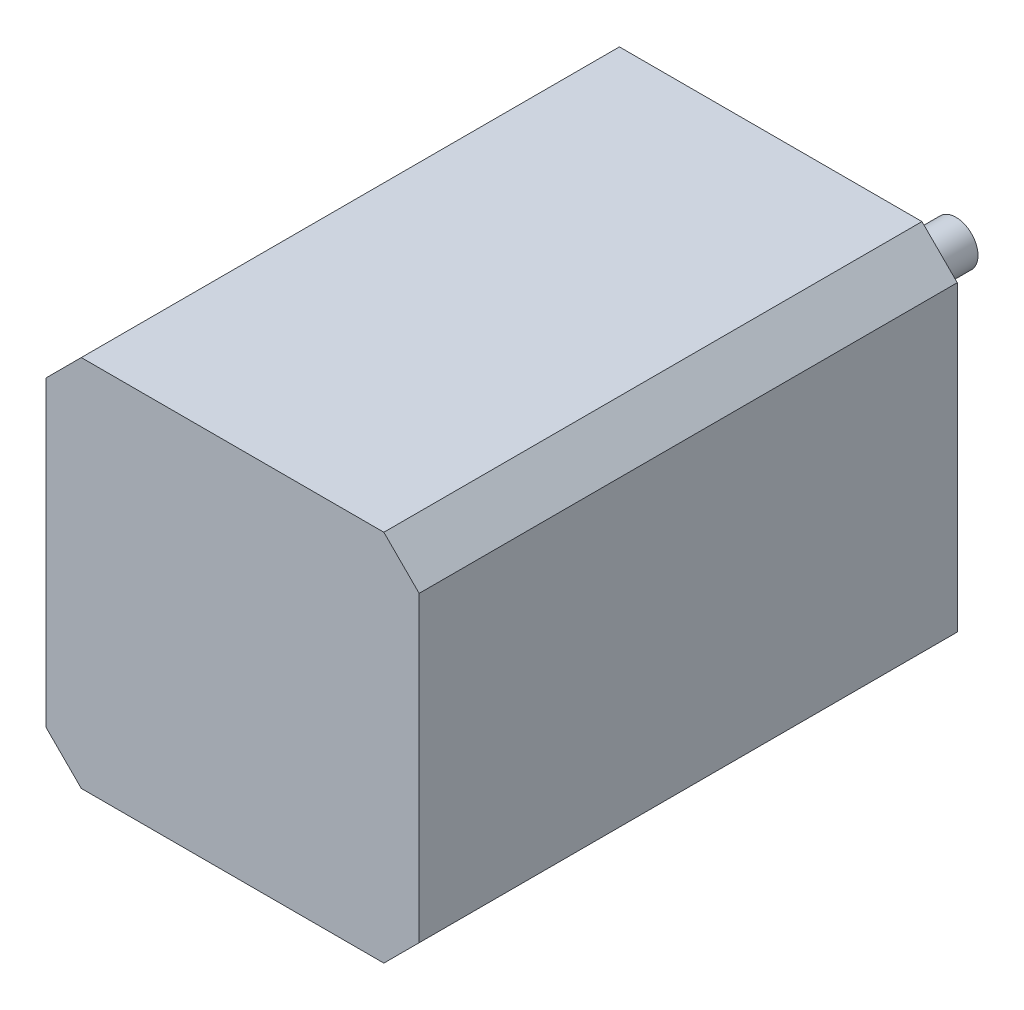
SolidWorks part; units mm, degrees
ref_plane "Front Plane" through (0, 0, 0) normal (0, 0, 1) x (1, 0, 0)
ref_plane "Top Plane" through (0, 0, 0) normal (0, 1, 0) x (1, 0, 0)
ref_plane "Right Plane" through (0, 0, 0) normal (1, 0, 0) x (0, 0, -1)
sketch "Sketch1" plane through (0, 0, 0) normal (0, 0, 1) x (1, 0, 0)
  line L1 (-12.7279, 12.7279) -> (12.7279, 12.7279) construction
  line L2 (-12.7279, 12.7279) -> (-12.7279, -12.7279) construction
  line L3 (-12.7279, -12.7279) -> (12.7279, -12.7279) construction
  line L4 (12.7279, 12.7279) -> (12.7279, -12.7279) construction
  line L5 (-21.15, 21.15) -> (21.15, 21.15)
  line L6 (-21.15, 21.15) -> (-21.15, -21.15)
  line L7 (-21.15, -21.15) -> (21.15, -21.15)
  line L8 (21.15, 21.15) -> (21.15, -21.15)
  circle A0 centre (0, 0) radius 11
  circle A1 centre (0, 0) radius 2.5
  circle A2 centre (-12.7279, 12.7279) radius 2
  circle A3 centre (12.7279, 12.7279) radius 2
  circle A4 centre (12.7279, -12.7279) radius 2
  circle A5 centre (-12.7279, -12.7279) radius 2
  circle A6 centre (0, 0) radius 18 construction
  point P12 (0, 12.7279)
  point P13 (-12.7279, 0)
  point P18 (0, -21.15)
  point P19 (-21.15, 0)
  dimension "D1" = 22
  dimension "D2" = 5
  dimension "D3" = 36
  dimension "D4" = 4
  dimension "D5" = 42.3
extrude "Boss-Extrude1" add sketch "Sketch1" along normal blind 61 contours L8 L5 L6 L7 A5 A4 A3 A2 A0 | A0 A1 | A5 | A2 | A3 | A4 | A1 region at (0, 20.5518, 0) region at (-10.6889, 0, 0) region at (0, 0, 0) region at (-12.7279, 12.7279, 0) region at (12.7279, 12.7279, 0) region at (12.7279, -12.7279, 0) region at (-12.7279, -12.7279, 0)
extrude "Boss-Extrude2" add sketch "Sketch1<3>" against normal blind 2 contours A0 A1 region at (-10.6889, 0, 0)
sketch "Sketch1<3>" plane through (0, 0, 0) normal (0, 0, 1) x (1, 0, 0) same geometry as "Sketch1"
extrude "Cut-Extrude1" cut sketch "Sketch1<4>" along normal blind 2 contours A3 | A2 | A5 | A4 region at (-12.7279, 12.7279, 0) region at (12.7279, 12.7279, 0) region at (12.7279, -12.7279, 0) region at (-12.7279, -12.7279, 0)
sketch "Sketch1<4>" plane through (0, 0, 0) normal (0, 0, 1) x (1, 0, 0) same geometry as "Sketch1"
extrude "Boss-Extrude3" add sketch "Sketch1<5>" against normal blind 19 from surface contours A1 region at (0, 0, 0) starting at face at (2.5, 0, -2)
sketch "Sketch1<5>" plane through (0, 0, 0) normal (0, 0, 1) x (1, 0, 0) same geometry as "Sketch1"
chamfer "Chamfer1" distance 4 angle 45 4 edges at (21.15, -21.15, 30.5) (21.15, 21.15, 30.5) (-21.15, 21.15, 30.5) (-21.15, -21.15, 30.5)
